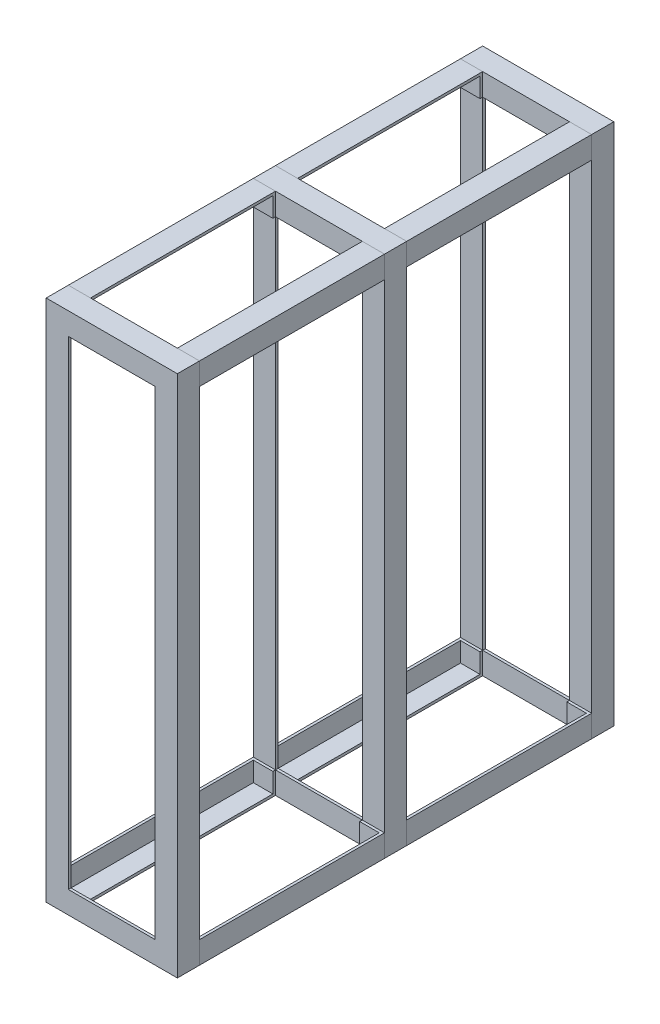
SolidWorks part; units mm, degrees
material "Gray Cast Iron"
ref_plane "Front Plane" through (0, 0, 0) normal (0, 0, 1) x (1, 0, 0)
ref_plane "Top Plane" through (0, 0, 0) normal (0, 1, 0) x (1, 0, 0)
ref_plane "Right Plane" through (0, 0, 0) normal (1, 0, 0) x (0, 0, -1)
sketch "Sketch1" plane through (0, 0, 0) normal (0, 1, 0) x (1, 0, 0)
  line L1 (12.7, -12.7) -> (-12.7, -12.7)
  line L2 (12.7, -12.7) -> (12.7, 12.7)
  line L3 (12.7, 12.7) -> (-12.7, 12.7)
  line L4 (-12.7, -12.7) -> (-12.7, 12.7)
  line L5 (12.7, -12.7) -> (-12.7, 12.7) construction
  line L6 (12.7, 12.7) -> (-12.7, -12.7) construction
  point P0 (0, 0)
  dimension "D1" = 25.4
  dimension "D2" = 25.4
extrude "Boss-Extrude1" add sketch "Sketch1" along normal blind 600
sketch "Sketch2" plane through (-12.7, 0, 0) normal (-1, 0, 0) x (0, 0, 1)
  line L0 (12.7, 600) -> (12.7, 0) construction
  line L1 (-12.7, 600) -> (12.7, 600)
  line L2 (-12.7, 600) -> (-12.7, 574.6)
  line L3 (-12.7, 574.6) -> (12.7, 574.6)
  line L4 (12.7, 600) -> (12.7, 574.6)
extrude "Boss-Extrude2" add sketch "Sketch2" along normal blind 125
sketch "Sketch3" plane through (0, 574.6, 0) normal (0, -1, 0) x (-1, 0, 0)
  line L0 (137.7, 12.7) -> (12.7, 12.7) construction
  line L1 (137.7, -12.7) -> (112.3, -12.7)
  line L2 (137.7, -12.7) -> (137.7, 12.7)
  line L3 (137.7, 12.7) -> (112.3, 12.7)
  line L4 (112.3, -12.7) -> (112.3, 12.7)
extrude "Boss-Extrude3" add sketch "Sketch3" along normal blind 574.6
sketch "Sketch4" plane through (0, 0, -12.7) normal (0, 0, -1) x (-1, 0, 0)
  line L0 (137.7, 600) -> (137.7, 0) construction
  line L1 (-12.7, 0) -> (137.7, 0)
  line L2 (-12.7, 0) -> (-12.7, 25.4)
  line L3 (-12.7, 25.4) -> (137.7, 25.4)
  line L4 (137.7, 0) -> (137.7, 25.4)
  dimension "D1" = 25.4
extrude "Boss-Extrude4" add sketch "Sketch4" against normal blind 25.4
sketch "Sketch5" plane through (0, 0, -12.7) normal (0, 0, -1) x (-1, 0, 0)
  line L1 (-12.7, 600) -> (12.7, 600)
  line L2 (-12.7, 600) -> (-12.7, 574.6)
  line L3 (-12.7, 574.6) -> (12.7, 574.6)
  line L4 (12.7, 600) -> (12.7, 574.6)
  line L5 (137.7, 600) -> (112.3, 600)
  line L6 (137.7, 600) -> (137.7, 574.6)
  line L7 (137.7, 574.6) -> (112.3, 574.6)
  line L8 (112.3, 600) -> (112.3, 574.6)
  line L9 (-12.7, 0) -> (12.7, 0)
  line L10 (-12.7, 0) -> (-12.7, 25.4)
  line L11 (-12.7, 25.4) -> (12.7, 25.4)
  line L12 (12.7, 0) -> (12.7, 25.4)
  line L13 (112.3, 25.4) -> (137.7, 25.4)
  line L14 (112.3, 25.4) -> (112.3, 0)
  line L15 (112.3, 0) -> (137.7, 0)
  line L16 (137.7, 25.4) -> (137.7, 0)
extrude "Boss-Extrude5" add sketch "Sketch5" along normal blind 212.1 separate body
sketch "Sketch6" plane through (0, 0, -224.8) normal (0, 0, -1) x (-1, 0, 0)
  line L0 (112.3, 574.6) -> (12.7, 574.6)
  line L1 (137.7, 0) -> (-12.7, 0)
  line L2 (137.7, 0) -> (137.7, 600)
  line L3 (137.7, 600) -> (-12.7, 600)
  line L4 (-12.7, 0) -> (-12.7, 600)
  line L5 (12.7, 25.4) -> (12.7, 574.6)
  line L6 (112.3, 25.4) -> (12.7, 25.4)
  line L7 (112.3, 25.4) -> (112.3, 574.6)
  dimension "D1" = 25.4
extrude "Boss-Extrude6" add sketch "Sketch6" along normal blind 25.4 separate body
sketch "Sketch7" plane through (0, 0, -250.2) normal (0, 0, -1) x (-1, 0, 0)
  line L1 (-12.7, 600) -> (12.7, 600)
  line L2 (-12.7, 600) -> (-12.7, 574.6)
  line L3 (-12.7, 574.6) -> (12.7, 574.6)
  line L4 (12.7, 600) -> (12.7, 574.6)
  line L5 (112.3, 574.6) -> (137.7, 574.6)
  line L6 (112.3, 574.6) -> (112.3, 600)
  line L7 (112.3, 600) -> (137.7, 600)
  line L8 (137.7, 574.6) -> (137.7, 600)
  line L9 (-12.7, 0) -> (12.7, 0)
  line L10 (-12.7, 0) -> (-12.7, 25.4)
  line L11 (-12.7, 25.4) -> (12.7, 25.4)
  line L12 (12.7, 0) -> (12.7, 25.4)
  line L13 (112.3, 25.4) -> (137.7, 25.4)
  line L14 (112.3, 25.4) -> (112.3, 0)
  line L15 (112.3, 0) -> (137.7, 0)
  line L16 (137.7, 25.4) -> (137.7, 0)
extrude "Boss-Extrude7" add sketch "Sketch7" along normal blind 212.1 separate body
sketch "Sketch9" plane through (0, 0, -462.3) normal (0, 0, -1) x (-1, 0, 0)
  line L0 (112.3, 574.6) -> (12.7, 574.6)
  line L1 (137.7, 0) -> (-12.7, 0)
  line L2 (137.7, 0) -> (137.7, 600)
  line L3 (137.7, 600) -> (-12.7, 600)
  line L4 (-12.7, 0) -> (-12.7, 600)
  line L5 (12.7, 25.4) -> (12.7, 574.6)
  line L6 (112.3, 25.4) -> (12.7, 25.4)
  line L7 (112.3, 25.4) -> (112.3, 574.6)
  dimension "D1" = 25.4
extrude "Boss-Extrude8" add sketch "Sketch9" along normal blind 25.4 separate body
shell "Shell2" thickness 3 removed face at (-112.3, 300, 0) removed face at (-62.5, 574.6, 0) removed face at (-62.5, 25.4, 0) removed face at (-12.7, 300, 0) removed face at (-62.5, 300, -12.7)
shell "Shell3" thickness 3 removed face at (0, 587.3, -12.7) removed face at (0, 574.6, -118.75) removed face at (-12.7, 587.3, -118.75)
shell "Shell4" thickness 3 removed face at (-125, 587.3, -12.7) removed face at (-112.3, 587.3, -118.75) removed face at (-125, 574.6, -118.75)
shell "Shell5" thickness 3 removed face at (0, 12.7, -12.7) removed face at (-12.7, 12.7, -118.75) removed face at (0, 25.4, -118.75)
shell "Shell6" thickness 3 removed face at (-125, 12.7, -12.7) removed face at (-112.3, 12.7, -118.75) removed face at (-125, 25.4, -118.75)
shell "Shell7" thickness 3 removed face at (-62.5, 300, -250.2) removed face at (-112.3, 300, -237.5) removed face at (-62.5, 25.4, -237.5) removed face at (-12.7, 300, -237.5) removed face at (-62.5, 574.6, -237.5)
shell "Shell8" thickness 3 removed face at (-125, 574.6, -356.25) removed face at (-112.3, 587.3, -356.25) removed face at (-125, 587.3, -250.2)
shell "Shell9" thickness 3 removed face at (0, 587.3, -250.2) removed face at (-12.7, 587.3, -356.25) removed face at (0, 574.6, -356.25)
shell "Shell10" thickness 3 removed face at (0, 25.4, -356.25) removed face at (-12.7, 12.7, -356.25) removed face at (0, 12.7, -250.2)
shell "Shell11" thickness 3 removed face at (-125, 12.7, -250.2) removed face at (-125, 25.4, -356.25) removed face at (-112.3, 12.7, -356.25)
shell "Shell12" thickness 3 removed face at (-62.5, 574.6, -475) removed face at (-112.3, 300, -475) removed face at (-62.5, 25.4, -475) removed face at (-62.5, 300, -487.7) removed face at (-12.7, 300, -475)
